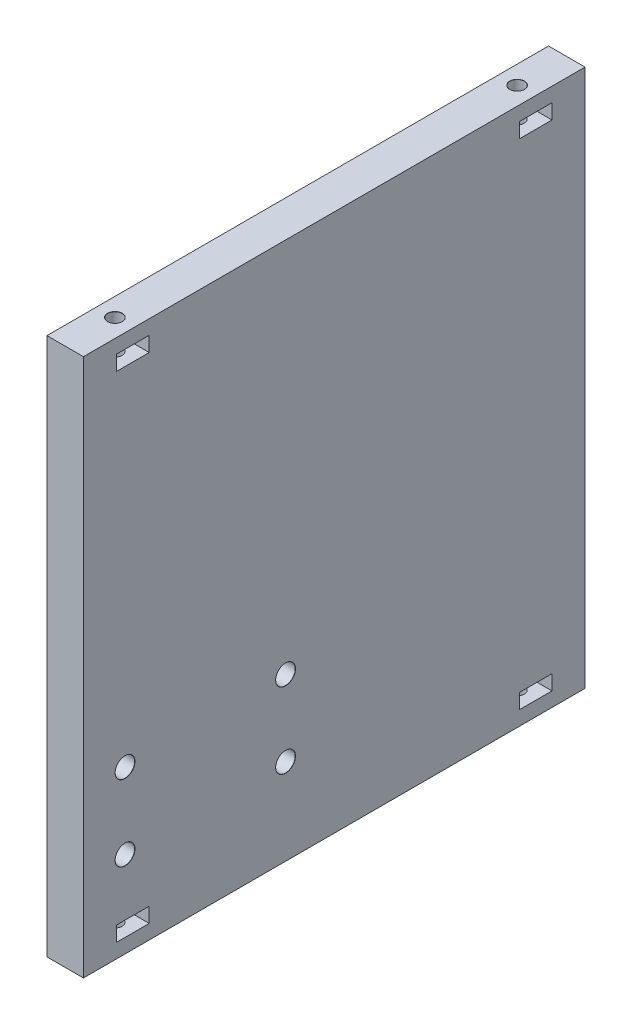
SolidWorks part; units mm, degrees
material "6061 Alloy"
ref_plane "Front Plane" through (0, 0, 0) normal (0, 0, 1) x (1, 0, 0)
ref_plane "Top Plane" through (0, 0, 0) normal (0, 1, 0) x (1, 0, 0)
ref_plane "Right Plane" through (0, 0, 0) normal (1, 0, 0) x (0, 0, -1)
sketch "Sketch1" plane through (0, 0, 0) normal (1, 0, 0) x (0, 0, -1)
  line L1 (-43.65, -46.825) -> (43.65, -46.825)
  line L2 (-43.65, -46.825) -> (-43.65, 46.825)
  line L3 (-43.65, 46.825) -> (43.65, 46.825)
  line L4 (43.65, -46.825) -> (43.65, 46.825)
  line L5 (-43.65, -46.825) -> (43.65, 46.825) construction
  line L6 (-43.65, 46.825) -> (43.65, -46.825) construction
  point P0 (0, 0)
extrude "Boss-Extrude1" add sketch "Sketch1" along normal blind 6.35
sketch "Sketch2" plane through (0, 46.825, 0) normal (0, 1, 0) x (1, 0, 0)
  line L0 (3.175, 43.65) -> (3.175, 35)
  line L1 (6.35, 43.65) -> (0, 43.65) construction
  line L2 (3.175, -43.65) -> (3.175, -35)
  line L3 (6.35, -43.65) -> (0, -43.65) construction
hole_wizard "Tap Drill for M3x0.5 Tap1" positions "Sketch3" profile "Sketch4" hole size "M3x0.5" standard "ANSI Metric"
sketch "Sketch3" plane through (0, 46.825, 0) normal (0, 1, 0) x (1, 0, 0)
  point P0 (3.175, 35)
  point P3 (3.175, -35)
sketch "Sketch4" plane through (3.175, 46.825, -35) normal (1, 0, 0) x (0, 0, 1)
  line L0 (0, 0) -> (0, 10.7511)
  line L1 (0, 10.7511) -> (1.25, 10)
  line L2 (1.25, 10) -> (1.25, 0.025)
  line L3 (1.25, 0.025) -> (1.275, 0)
  line L5 (1.275, 0) -> (0, 0)
  line L6 (-1.25, 0.025) -> (-1.275, 0) construction
  line L10 (0, 10.7511) -> (-1.25, 10) construction
  line L11 (0, -6.35) -> (0, 107.95) construction
  dimension "Hole Dia." = 2.5
  dimension "Hole Depth" = 10
  dimension "Near C'Sink Dia." = 2.55
  dimension "Near C'Sink Angle" = 90
  dimension "Drill Angle" = 118
sketch "Sketch5" plane through (0, -46.825, 0) normal (0, -1, 0) x (1, 0, 0)
  line L0 (3.175, 43.65) -> (3.175, 35)
  line L1 (3.175, -43.65) -> (3.175, -35)
  line L2 (6.35, -43.65) -> (0, -43.65) construction
hole_wizard "Tap Drill for M3x0.5 Tap2" positions "Sketch6" profile "Sketch7" hole size "M3x0.5" standard "ANSI Metric"
sketch "Sketch6" plane through (0, -46.825, 0) normal (0, -1, 0) x (-1, 0, 0)
  point P0 (-3.175, -35)
  point P3 (-3.175, 35)
sketch "Sketch7" plane through (3.175, -46.825, 35) normal (1, 0, 0) x (0, 0, -1)
  line L0 (0, 0) -> (0, 10)
  line L1 (0, 10) -> (1.25, 9.2489)
  line L2 (1.25, 9.2489) -> (1.25, 0.025)
  line L3 (1.25, 0.025) -> (1.275, 0)
  line L5 (1.275, 0) -> (0, 0)
  line L6 (-1.25, 0.025) -> (-1.275, 0) construction
  line L10 (0, 10) -> (-1.25, 9.2489) construction
  line L11 (0, -6.35) -> (0, 107.95) construction
  dimension "Hole Dia." = 2.5
  dimension "Hole Depth" = 10
  dimension "Near C'Sink Dia." = 2.55
  dimension "Near C'Sink Angle" = 90
  dimension "Drill Angle" = 118
sketch "Sketch8" plane through (6.35, 0, 0) normal (1, 0, 0) x (0, 0, -1)
  line L0 (-43.65, -46.825) -> (-43.65, -31.825)
  line L1 (-43.65, 46.825) -> (-43.65, -46.825) construction
  line L2 (-43.65, -31.825) -> (-36.41, -31.825)
  line L3 (-36.41, -31.825) -> (-8.47, -31.825)
  line L4 (-36.41, -31.825) -> (-36.41, -18.655)
  line L5 (-8.47, -31.825) -> (-8.47, -18.655)
hole_wizard "M3 Clearance Hole1" positions "Sketch9" profile "Sketch10" hole size "M3" standard "ANSI Metric" end condition through all
sketch "Sketch9" plane through (6.35, 0, 0) normal (1, 0, 0) x (0, 0, -1)
  point P0 (-36.41, -18.655)
  point P3 (-8.47, -18.655)
  point P6 (-8.47, -31.825)
  point P9 (-36.41, -31.825)
sketch "Sketch10" plane through (6.35, -18.655, 36.41) normal (0, 1, 0) x (0, 0, -1)
  line L0 (0, 0) -> (0, 6.35)
  line L1 (0, 6.35) -> (1.7, 6.35)
  line L2 (1.7, 6.35) -> (1.7, 0.025)
  line L3 (1.7, 0.025) -> (1.725, 0)
  line L5 (1.725, 0) -> (0, 0)
  line L6 (-1.7, 0.025) -> (-1.725, 0) construction
  line L11 (0, -6.35) -> (0, 107.95) construction
  dimension "Thru Hole Dia." = 3.4
  dimension "Thru Hole Depth" = 6.35
  dimension "Near C'Sink Dia." = 3.45
  dimension "Near C'Sink Angle" = 90
sketch "Sketch11" plane through (6.35, 0, -6.35) normal (-1, 0, 0) x (0, 0, 1)
  line L4 (37.7453, 51.4897) -> (45.0547, 51.4897) construction
  line L5 (-21.125, 46.825) -> (-36.275, 46.825) construction
  line L6 (42.65, -55.1957) -> (40.15, -55.1957) construction
  line L7 (-20.1, -46.825) -> (-37.3, -46.825) construction
  line L8 (-37.3, 46.825) -> (50, 46.825) construction
  line L9 (38.55, -44.325) -> (44.25, -44.325)
  line L10 (38.55, -44.325) -> (38.55, -41.725)
  line L11 (38.55, -41.725) -> (44.25, -41.725)
  line L12 (44.25, -44.325) -> (44.25, -41.725)
  line L13 (38.55, -44.325) -> (44.25, -41.725) construction
  line L14 (38.55, -41.725) -> (44.25, -44.325) construction
  line L15 (-31.55, -44.325) -> (-25.85, -44.325)
  line L16 (-31.55, -44.325) -> (-31.55, -41.725)
  line L17 (-31.55, -41.725) -> (-25.85, -41.725)
  line L18 (-25.85, -44.325) -> (-25.85, -41.725)
  line L19 (-31.55, -44.325) -> (-25.85, -41.725) construction
  line L20 (-31.55, -41.725) -> (-25.85, -44.325) construction
  line L21 (-31.55, 44.325) -> (-25.85, 44.325)
  line L22 (-31.55, 44.325) -> (-31.55, 41.725)
  line L23 (-31.55, 41.725) -> (-25.85, 41.725)
  line L24 (-25.85, 44.325) -> (-25.85, 41.725)
  line L25 (-31.55, 44.325) -> (-25.85, 41.725) construction
  line L26 (-31.55, 41.725) -> (-25.85, 44.325) construction
  line L27 (38.55, 44.325) -> (44.25, 44.325)
  line L28 (38.55, 44.325) -> (38.55, 41.725)
  line L29 (38.55, 41.725) -> (44.25, 41.725)
  line L30 (44.25, 44.325) -> (44.25, 41.725)
  line L31 (38.55, 44.325) -> (44.25, 41.725) construction
  line L32 (38.55, 41.725) -> (44.25, 44.325) construction
  line L33 (50, -46.825) -> (-37.3, -46.825) construction
  line L34 (-37.3, -46.825) -> (-37.3, 46.825) construction
  line L35 (50, 46.825) -> (50, -46.825) construction
  point P8 (41.4, -43.025)
  point P13 (-28.7, -43.025)
  point P18 (-28.7, 43.025)
  point P23 (41.4, 43.025)
  point P28 (37.4047, 35.8827)
  point P29 (-28.7, 46.825)
  point P30 (-28.7, -46.825)
  point P31 (41.4, -55.1957)
  point P32 (41.4, 51.4897)
  point P33 (-28.7, -44.325)
  point P38 (0, 0)
  point P40 (0, 0)
  point P41 (0, 0)
  point P46 (0, 0)
  point P47 (0, 0)
  point P48 (0, 0)
  dimension "D1" = 2.5
  dimension "D2" = 2.5
  dimension "D3" = 5.7
  dimension "D4" = 2.6
  dimension "D5" = 5.75
  dimension "D6" = 5.75
extrude "Cut-Extrude3" cut sketch "Sketch11" along normal through all contours L12 L9 L10 L11 | L27 L30 L29 L28 | L21 L24 L23 L22 | L18 L15 L16 L17 region at (6.35, -43.025, 35.05) region at (6.35, -43.025, -35.05) region at (6.35, 43.025, -35.05) region at (6.35, 43.025, 35.05)
